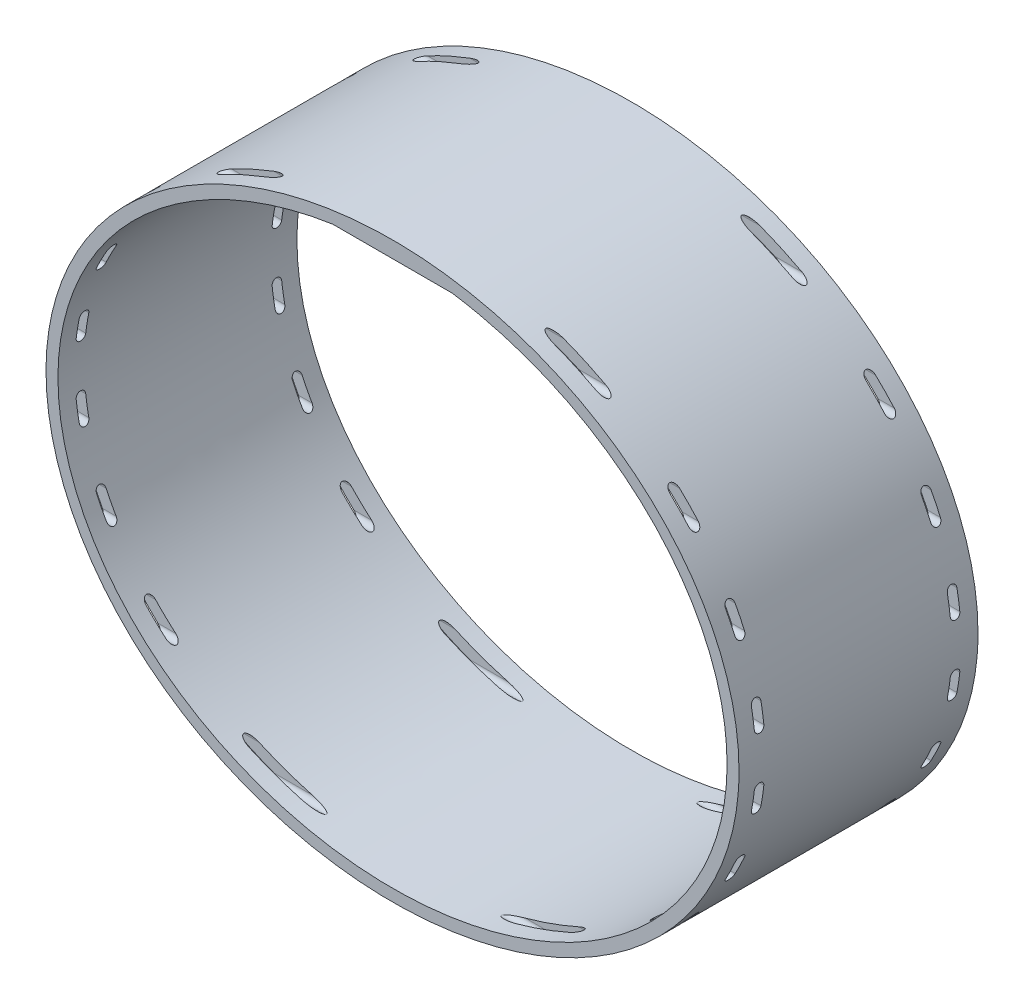
SolidWorks part; units mm, degrees
ref_plane "Front Plane" through (0, 0, 0) normal (0, 0, 1) x (1, 0, 0)
ref_plane "Top Plane" through (0, 0, 0) normal (0, 1, 0) x (1, 0, 0)
ref_plane "Right Plane" through (0, 0, 0) normal (1, 0, 0) x (0, 0, -1)
sketch "Sketch1" plane through (0, 0, 0) normal (0, 0, 1) x (1, 0, 0)
  line L3 (-140, 0) -> (140, 0) construction
  line L16 (0, -115) -> (0, 115) construction
  line L17 (25, 113.1516) -> (-25, 113.1516)
  ellipse E0 centre (0, 0) end of major axis (140, 0) minor radius 115 (-25, 113.1516) -> (25, 113.1516) ccw
  spline S1 degree 3 poles (143.0982, -23.7749) (145.9509, 0) (143.0982, 23.7749) (134.6733, 46.5733) (121.0543, 67.4909) (102.8167, 85.7372) (80.6906, 100.6456) (47.149, 115.376) (0, 123.0827) (-47.149, 115.376) (-80.6906, 100.6456) (-102.8167, 85.7372) (-121.0543, 67.4909) (-134.6733, 46.5733) (-143.0982, 23.7749) (-145.9509, 0) (-143.0982, -23.7749) (-134.6733, -46.5733) (-121.0543, -67.4909) (-102.8167, -85.7372) (-80.6906, -100.6456) (-47.149, -115.376) (0, -123.0827) (47.149, -115.376) (80.6906, -100.6456) (102.8167, -85.7372) (121.0543, -67.4909) (134.6733, -46.5733) (143.0982, -23.7749) (145.9509, 0) (143.0982, 23.7749) knots -0.589049 -0.392699 -0.19635 0 0.19635 0.392699 0.589049 0.785398 0.981748 1.178097 1.570796 1.963495 2.159845 2.356194 2.552544 2.748894 2.945243 3.141593 3.337942 3.534292 3.730641 3.926991 4.12334 4.31969 4.712389 5.105088 5.301438 5.497787 5.694137 5.890486 6.086836 6.283185 6.479535 6.675884 6.872234 only from (145, 0) to (145, 0)
  dimension "D1" = 280
  dimension "D2" = 230
  dimension "D3" = 50
extrude "Boss-Extrude1" add sketch "Sketch1" along normal mid plane 100
sketch "Sketch2" plane through (0, 0, 0) normal (1, 0, 0) x (0, 0, -1)
  line L0 (0, 120) -> (0, -120) construction
  line L1 (50, 120) -> (-50, 120) construction
  line L2 (-50, -120) -> (50, -120) construction
  line L3 (41, -101) -> (41, -109) construction
  line L4 (43, -101) -> (43, -109)
  line L5 (39, -101) -> (39, -109)
  line L6 (41, -71) -> (41, -79) construction
  line L7 (43, -71) -> (43, -79)
  line L8 (39, -71) -> (39, -79)
  line L9 (41, -41) -> (41, -49) construction
  line L10 (43, -41) -> (43, -49)
  line L11 (39, -41) -> (39, -49)
  line L12 (41, -11) -> (41, -19) construction
  line L13 (43, -11) -> (43, -19)
  line L14 (39, -11) -> (39, -19)
  line L15 (41, 19) -> (41, 11) construction
  line L16 (43, 19) -> (43, 11)
  line L17 (39, 19) -> (39, 11)
  line L18 (41, 49) -> (41, 41) construction
  line L19 (43, 49) -> (43, 41)
  line L20 (39, 49) -> (39, 41)
  line L21 (41, 79) -> (41, 71) construction
  line L22 (43, 79) -> (43, 71)
  line L23 (39, 79) -> (39, 71)
  line L24 (41, 109) -> (41, 101) construction
  line L25 (43, 109) -> (43, 101)
  line L26 (39, 109) -> (39, 101)
  line L27 (0, 0) -> (50, 0) construction
  line L28 (50, -120) -> (50, 120) construction
  line L29 (-41, -101) -> (-41, -109) construction
  line L30 (-43, -101) -> (-43, -109)
  line L31 (-39, -101) -> (-39, -109)
  line L32 (-41, -71) -> (-41, -79) construction
  line L33 (-43, -71) -> (-43, -79)
  line L34 (-39, -71) -> (-39, -79)
  line L35 (-41, -41) -> (-41, -49) construction
  line L36 (-43, -41) -> (-43, -49)
  line L37 (-39, -41) -> (-39, -49)
  line L38 (-41, -11) -> (-41, -19) construction
  line L39 (-43, -11) -> (-43, -19)
  line L40 (-39, -11) -> (-39, -19)
  line L41 (-41, 19) -> (-41, 11) construction
  line L42 (-43, 19) -> (-43, 11)
  line L43 (-39, 19) -> (-39, 11)
  line L44 (-41, 49) -> (-41, 41) construction
  line L45 (-43, 49) -> (-43, 41)
  line L46 (-39, 49) -> (-39, 41)
  line L47 (-41, 79) -> (-41, 71) construction
  line L48 (-43, 79) -> (-43, 71)
  line L49 (-39, 79) -> (-39, 71)
  line L50 (-41, 109) -> (-41, 101) construction
  line L51 (-43, 109) -> (-43, 101)
  line L52 (-39, 109) -> (-39, 101)
  arc A0 (43, -101) -> (39, -101) centre (41, -101) ccw
  arc A1 (39, -109) -> (43, -109) centre (41, -109) ccw
  arc A2 (43, -71) -> (39, -71) centre (41, -71) ccw
  arc A3 (39, -79) -> (43, -79) centre (41, -79) ccw
  arc A4 (43, -41) -> (39, -41) centre (41, -41) ccw
  arc A5 (39, -49) -> (43, -49) centre (41, -49) ccw
  arc A6 (43, -11) -> (39, -11) centre (41, -11) ccw
  arc A7 (39, -19) -> (43, -19) centre (41, -19) ccw
  arc A8 (43, 19) -> (39, 19) centre (41, 19) ccw
  arc A9 (39, 11) -> (43, 11) centre (41, 11) ccw
  arc A10 (43, 49) -> (39, 49) centre (41, 49) ccw
  arc A11 (39, 41) -> (43, 41) centre (41, 41) ccw
  arc A12 (43, 79) -> (39, 79) centre (41, 79) ccw
  arc A13 (39, 71) -> (43, 71) centre (41, 71) ccw
  arc A14 (43, 109) -> (39, 109) centre (41, 109) ccw
  arc A15 (39, 101) -> (43, 101) centre (41, 101) ccw
  arc A16 (-43, -101) -> (-39, -101) centre (-41, -101) cw
  arc A17 (-39, -109) -> (-43, -109) centre (-41, -109) cw
  arc A18 (-43, -71) -> (-39, -71) centre (-41, -71) cw
  arc A19 (-39, -79) -> (-43, -79) centre (-41, -79) cw
  arc A20 (-43, -41) -> (-39, -41) centre (-41, -41) cw
  arc A21 (-39, -49) -> (-43, -49) centre (-41, -49) cw
  arc A22 (-43, -11) -> (-39, -11) centre (-41, -11) cw
  arc A23 (-39, -19) -> (-43, -19) centre (-41, -19) cw
  arc A24 (-43, 19) -> (-39, 19) centre (-41, 19) cw
  arc A25 (-39, 11) -> (-43, 11) centre (-41, 11) cw
  arc A26 (-43, 49) -> (-39, 49) centre (-41, 49) cw
  arc A27 (-39, 41) -> (-43, 41) centre (-41, 41) cw
  arc A28 (-43, 79) -> (-39, 79) centre (-41, 79) cw
  arc A29 (-39, 71) -> (-43, 71) centre (-41, 71) cw
  arc A30 (-43, 109) -> (-39, 109) centre (-41, 109) cw
  arc A31 (-39, 101) -> (-43, 101) centre (-41, 101) cw
  point P8 (41, -105)
  point P13 (41, -99)
  point P14 (41, -111)
  point P18 (41, -75)
  point P23 (41, -69)
  point P24 (41, -81)
  point P27 (41, -45)
  point P32 (41, -39)
  point P33 (41, -51)
  point P36 (41, -15)
  point P41 (41, -9)
  point P42 (41, -21)
  point P45 (41, 15)
  point P50 (41, 21)
  point P51 (41, 9)
  point P54 (41, 45)
  point P59 (41, 51)
  point P60 (41, 39)
  point P63 (41, 75)
  point P68 (41, 81)
  point P69 (41, 69)
  point P72 (41, 105)
  point P77 (41, 111)
  point P78 (41, 99)
  point P86 (-41, -105)
  point P93 (-41, -75)
  point P100 (-41, -45)
  point P107 (-41, -15)
  point P114 (-41, 15)
  point P121 (-41, 45)
  point P128 (-41, 75)
  point P135 (-41, 105)
  point P140 (-41, 99)
  point P141 (-41, 111)
  point P142 (-41, 69)
  point P143 (-41, 81)
  point P144 (-41, 39)
  point P145 (-41, 51)
  point P146 (-41, 9)
  point P147 (-41, 21)
  point P148 (-41, -21)
  point P149 (-41, -9)
  point P150 (-41, -51)
  point P151 (-41, -39)
  point P152 (-41, -81)
  point P153 (-41, -69)
  point P154 (-41, -111)
  point P155 (-41, -99)
  dimension "D1" = 12
  dimension "D2" = 4
  dimension "D3" = 41
  dimension "D5" = 15
  dimension "D4" = 8
extrude "Cut-Extrude1" cut sketch "Sketch2" against normal through all both and the other way through all
